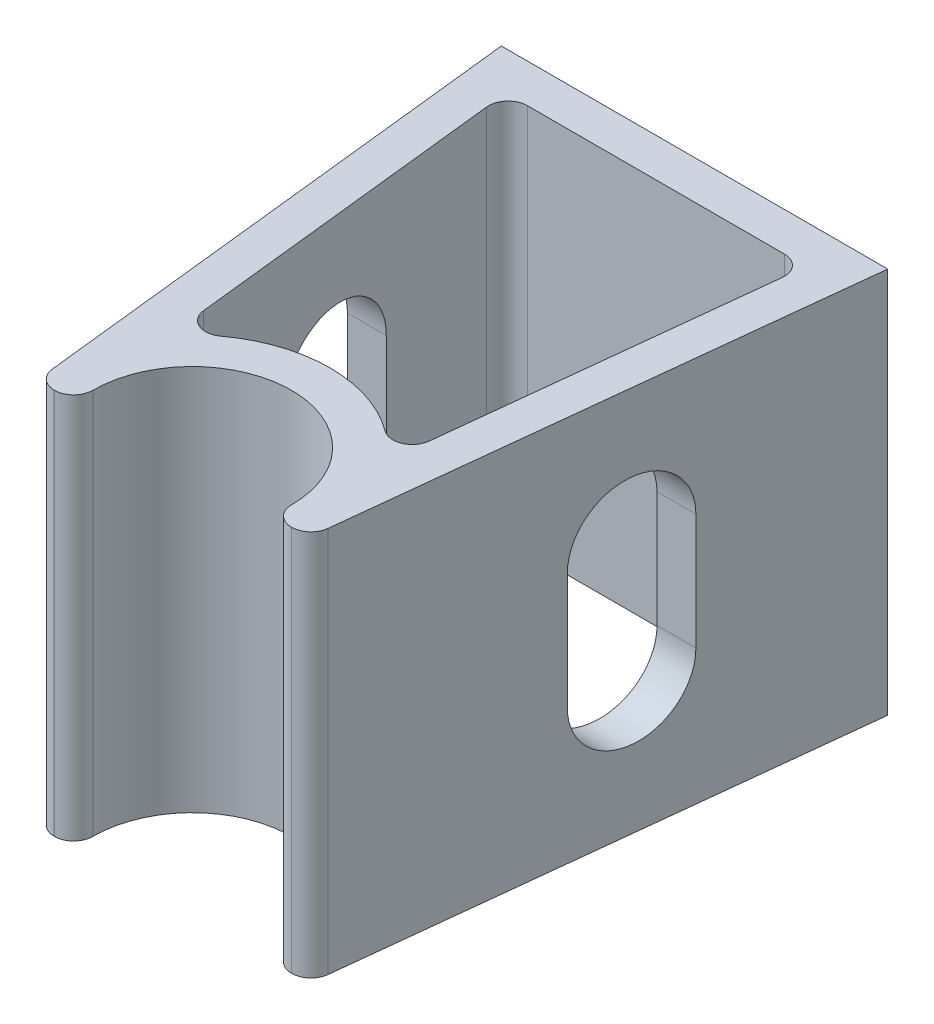
SolidWorks part; units mm, degrees
material "ABS"
ref_plane "Front Plane" through (0, 0, 0) normal (0, 0, 1) x (1, 0, 0)
ref_plane "Top Plane" through (0, 0, 0) normal (0, 1, 0) x (1, 0, 0)
ref_plane "Right Plane" through (0, 0, 0) normal (1, 0, 0) x (0, 0, -1)
sketch "Sketch1" plane through (0, 0, 0) normal (0, 1, 0) x (1, 0, 0)
  line L0 (-12.6, -2.5) -> (-17.6, -2.5)
  line L1 (-17.6, -2.5) -> (-25, 65)
  line L2 (-25, 65) -> (25, 65)
  line L3 (25, 65) -> (17.6, -2.5)
  line L4 (17.6, -2.5) -> (12.6, -2.5)
  arc A0 (12.6, -2.5) -> (-12.6, -2.5) centre (0, 0) ccw
  point P4 (0, 12.8456)
  dimension "D1" = 25.2
  dimension "D2" = 5
  dimension "D3" = 65
  dimension "D4" = 50
  dimension "D5" = 2.5
extrude "Boss-Extrude1" add sketch "Sketch1" along normal blind 50
sketch "Sketch2" plane through (0, 50, 0) normal (0, 1, 0) x (1, 0, 0)
  line L10 (14.0503, 11.0025) -> (19.4219, 60)
  line L11 (19.4219, 60) -> (-19.4219, 60)
  line L12 (-19.4219, 60) -> (-14.0503, 11.0025)
  line L13 (14.0503, 11.0025) -> (19.4219, 60)
  line L14 (19.4219, 60) -> (-19.4219, 60)
  line L15 (-19.4219, 60) -> (-14.0503, 11.0025)
  arc A2 (14.0503, 11.0025) -> (-14.0503, 11.0025) centre (0, 0) ccw
  arc A3 (14.0503, 11.0025) -> (-14.0503, 11.0025) centre (0, 0) ccw
  dimension "D1" = 5
extrude "Cut-Extrude1" cut sketch "Sketch2" against normal through all both and the other way through all
fillet "Fillet2" radius 2.5 8 edges at (-19.4219, 25, -60) (19.4219, 25, -60) (14.0503, 25, -11.0025) (-14.0503, 25, -11.0025) (17.6, 25, 2.5) (12.6, 25, 2.5) (-17.6, 25, 2.5) (-12.6, 25, 2.5)
sketch "Sketch3" plane through (0, 0, 0) normal (1, 0, 0) x (0, 0, -1)
  line L0 (35.1276, 0) -> (35.1276, 50) construction
  line L1 (-0.2724, 0) -> (65, 0) construction
  line L2 (-0.2724, 50) -> (65, 50) construction
  line L3 (35.1276, 32.5) -> (35.1276, 17.5) construction
  line L4 (42.6276, 32.5) -> (42.6276, 17.5)
  line L5 (27.6276, 32.5) -> (27.6276, 17.5)
  arc A1 (42.6276, 32.5) -> (27.6276, 32.5) centre (35.1276, 32.5) ccw
  arc A2 (27.6276, 17.5) -> (42.6276, 17.5) centre (35.1276, 17.5) ccw
  point P10 (35.1276, 25)
  dimension "D1" = 35.4
  dimension "D2" = 15
  dimension "D3" = 15
extrude "Cut-Extrude2" cut sketch "Sketch3" against normal through all both and the other way through all
sketch "Sketch4" plane through (0, 0, -65) normal (0, 0, -1) x (-1, 0, 0)
  text T0 "Koa Liles"
extrude "Boss-Extrude2" add sketch "Sketch4" along normal blind 1
